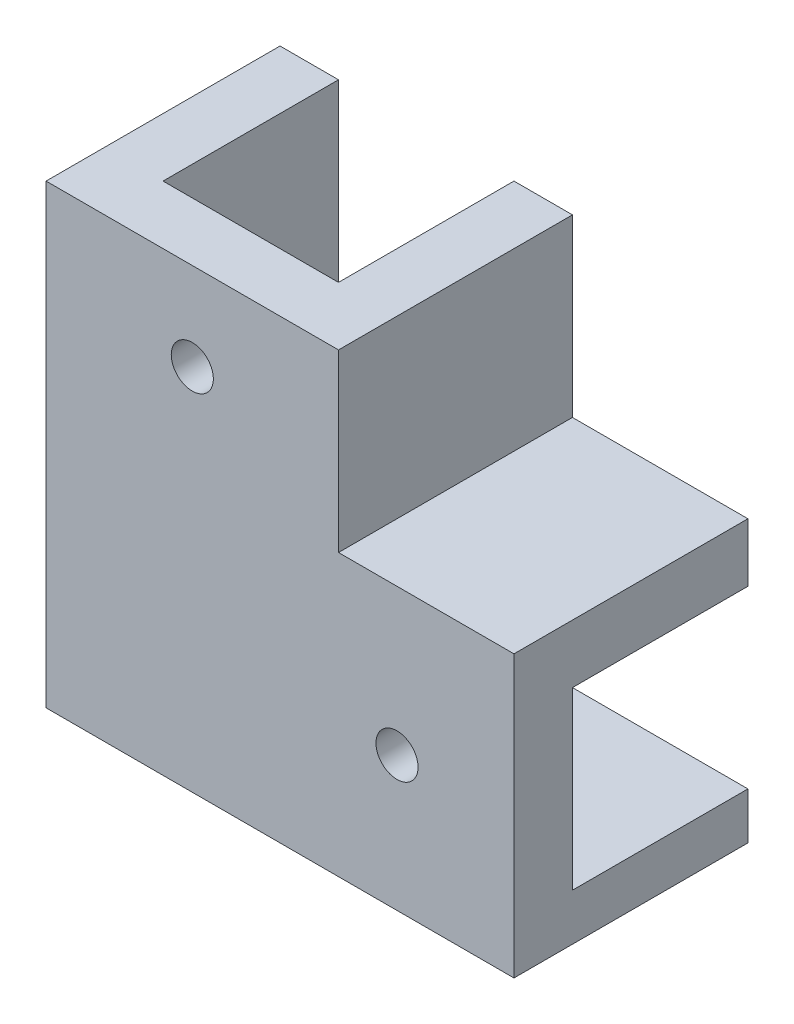
SolidWorks part; units mm, degrees
ref_plane "前视基准面" through (0, 0, 0) normal (0, 0, 1) x (1, 0, 0)
ref_plane "上视基准面" through (0, 0, 0) normal (0, 1, 0) x (1, 0, 0)
ref_plane "右视基准面" through (0, 0, 0) normal (1, 0, 0) x (0, 0, -1)
sketch "Sketch1" plane through (0, 0, 0) normal (0, 0, 1) x (1, 0, 0)
  line L0 (-7.5299, -25.8068) -> (27.4701, -25.8068)
  line L3 (-7.5299, 9.1932) -> (7.4701, 9.1932)
  line L4 (-7.5299, 9.1932) -> (-7.5299, -25.8068)
  line L6 (7.4701, 9.1932) -> (7.4701, -10.8068)
  line L7 (27.4701, -25.8068) -> (27.4701, -10.8068)
  line L8 (27.4701, -10.8068) -> (7.4701, -10.8068)
  dimension "D1" = 15
  dimension "D2" = 35
  dimension "D3" = 35
  dimension "D4" = 15
extrude "Boss-Extrude1" add sketch "Sketch1" along normal blind 5
sketch "Sketch2" plane through (0, 0, 0) normal (0, 0, -1) x (-1, 0, 0)
  line L0 (-7.4701, 9.1932) -> (-12.4701, 9.1932)
  line L1 (-12.4701, 9.1932) -> (-12.4701, -5.8068)
  line L2 (-12.4701, -5.8068) -> (-27.4701, -5.8068)
  line L3 (-27.4701, -10.8068) -> (-27.4701, -5.8068)
  line L4 (-27.4701, -10.8068) -> (-7.4701, -10.8068)
  line L5 (-7.4701, -10.8068) -> (-7.4701, 9.1932)
  dimension "D1" = 5
  dimension "D2" = 5
extrude "Boss-Extrude2" add sketch "Sketch2" along normal blind 15 separate body
sketch "Sketch3" plane through (0, 0, 0) normal (0, 0, -1) x (-1, 0, 0)
  line L0 (7.5299, 9.1932) -> (12.5299, 9.1932)
  line L1 (7.5299, -25.8068) -> (12.5299, -25.8068)
  line L2 (12.5299, -25.8068) -> (12.5299, 9.1932)
  line L3 (7.5299, -25.8068) -> (7.5299, 9.1932)
  dimension "D1" = 5
extrude "Boss-Extrude3" add sketch "Sketch3" along normal blind 15 separate body
sketch "Sketch4" plane through (0, 0, 0) normal (0, 0, 1) x (1, 0, 0)
  line L1 (-12.5299, 9.1932) -> (-7.5299, 9.1932)
  line L2 (-12.5299, 9.1932) -> (-12.5299, -25.8068)
  line L3 (-12.5299, -25.8068) -> (-7.5299, -25.8068)
  line L4 (-7.5299, 9.1932) -> (-7.5299, -25.8068)
extrude "Boss-Extrude4" add sketch "Sketch4" along normal blind 5
sketch "Sketch5" plane through (0, 0, 0) normal (0, 0, 1) x (1, 0, 0)
  line L0 (7.4701, 9.1932) -> (7.4701, -10.8068)
  line L1 (7.4701, -10.8068) -> (27.4701, -10.8068)
  line L2 (27.4701, -10.8068) -> (27.4701, -5.8068)
  line L3 (27.4701, -5.8068) -> (12.4701, -5.8068)
  line L4 (12.4701, -5.8068) -> (12.4701, 9.1932)
  line L5 (12.4701, 9.1932) -> (7.4701, 9.1932)
extrude "Boss-Extrude5" add sketch "Sketch5" along normal blind 5
sketch "Sketch7" plane through (0, 0, 0) normal (0, 0, -1) x (-1, 0, 0)
  line L0 (-27.4701, -25.8068) -> (-27.4701, -10.8068) construction
  line L1 (-27.4701, -10.8068) -> (-7.4701, -10.8068) construction
  line L2 (-7.4701, 9.1932) -> (7.5299, 9.1932) construction
  line L3 (7.5299, 9.1932) -> (7.5299, -25.8068) construction
  circle A0 centre (0.0299, 1.6932) radius 1.8
  circle A1 centre (-17.4701, -18.3068) radius 1.8
  dimension "D1" = 3.6
  dimension "D2" = 3.6
  dimension "D3" = 10
  dimension "D5" = 7.5
  dimension "D6" = 7.5
  dimension "D4" = 7.5
extrude "Cut-Extrude1" cut sketch "Sketch7" against normal through all
sketch "Sketch8" plane through (0, 0, -15) normal (0, 0, -1) x (-1, 0, 0)
  line L0 (12.5299, 9.1932) -> (-12.4701, 9.1932)
  line L1 (-12.4701, 9.1932) -> (-12.4701, -5.8068)
  line L2 (-12.4701, -5.8068) -> (-27.4701, -5.8068)
  line L3 (-27.4701, -5.8068) -> (-27.4701, -10.8068) construction
  line L4 (-27.4701, -5.8068) -> (-27.4701, -25.8068)
  line L5 (-27.4701, -25.8068) -> (12.5299, -25.8068)
  line L6 (12.5299, -25.8068) -> (12.5299, 9.1932)
sketch "Sketch9" plane through (0, 0, -15) normal (0, 0, -1) x (-1, 0, 0)
  line L0 (12.5299, -10.8068) -> (7.5299, -10.8068)
  line L2 (7.5299, -10.8068) -> (7.5299, -25.8068)
  line L3 (7.5299, -25.8068) -> (12.5299, -25.8068)
  line L4 (12.5299, -10.8068) -> (12.5299, -25.8068)
  dimension "D1" = 15
extrude "Boss-Extrude6" add sketch "Sketch9" along normal blind 10
sketch "Sketch10" plane through (0, -25.8068, 0) normal (0, -1, 0) x (1, 0, 0)
  line L0 (-7.5299, -25) -> (-7.5299, 0) construction
  line L1 (-7.5299, 0) -> (7.4701, 0)
  line L2 (-7.5299, 0) -> (-7.5299, -25)
  line L3 (-7.5299, -25) -> (7.4701, -25)
  line L4 (7.4701, 0) -> (7.4701, -25)
  dimension "D1" = 15
sketch "Sketch12" plane through (0, -25.8068, 0) normal (0, -1, 0) x (1, 0, 0)
  line L5 (7.4701, -25) -> (-12.5299, -25)
  line L6 (7.4701, -25) -> (7.4701, -15)
  line L7 (7.4701, 5) -> (-12.5299, 5)
  line L8 (-12.5299, -25) -> (-12.5299, 5)
  line L9 (27.4701, 5) -> (7.4701, 5)
  line L10 (27.4701, 5) -> (27.4701, -15)
  line L11 (27.4701, -15) -> (7.4701, -15)
extrude "Boss-Extrude7" add sketch "Sketch12" along normal blind 4
sketch "Sketch13" plane through (0, -29.8068, 0) normal (0, -1, 0) x (1, 0, 0)
  line L0 (-7.5299, -25) -> (7.4701, -25) construction
  line L1 (7.4701, 0) -> (7.4701, -25) construction
  circle A0 centre (-0.0299, -20) radius 1.5
  dimension "D1" = 3
  dimension "D2" = 5
  dimension "D3" = 7.5
extrude "Cut-Extrude4" cut sketch "Sketch13" against normal through all
